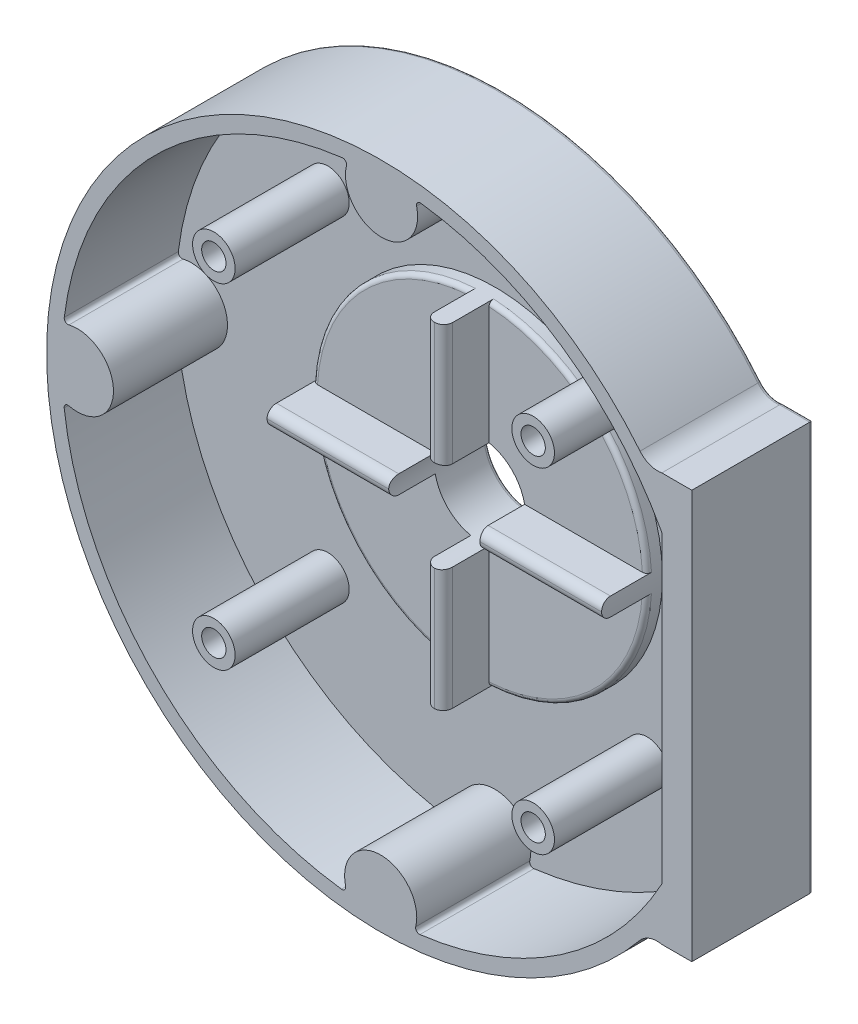
SolidWorks part; units mm, degrees
material "ABS"
ref_plane "Front Plane" through (0, 0, 0) normal (0, 0, 1) x (1, 0, 0)
ref_plane "Top Plane" through (0, 0, 0) normal (0, 1, 0) x (1, 0, 0)
ref_plane "Right Plane" through (0, 0, 0) normal (1, 0, 0) x (0, 0, -1)
sketch "Sketch2" plane through (0, 0, 0) normal (0, 0, 1) x (1, 0, 0)
  circle A0 centre (0, 0) radius 22
  dimension "D1" = 44
extrude "Boss-Extrude1" add sketch "Sketch2" along normal blind 8
sketch "Sketch3" plane through (0, 0, 8) normal (0, 0, 1) x (1, 0, 0)
  circle A0 centre (0, 0) radius 21
  dimension "D1" = 42
extrude "Cut-Extrude2" cut sketch "Sketch3" against normal blind 7.5
sketch "Sketch4" plane through (0, 0, 0.5) normal (0, 0, 1) x (1, 0, 0)
  line L0 (-11, -11.015) -> (10, -11.015) construction
  line L1 (-11, 11) -> (10, 11) construction
  line L2 (10, 11) -> (10, -11.015) construction
  line L3 (-11, 11) -> (0, 0) construction
  line L4 (0, 0) -> (10, -11.015) construction
  line L5 (10, 11) -> (0, 0) construction
  line L6 (0, 0) -> (-11, -11.015) construction
  line L8 (-11, 11) -> (-11, -11.015) construction
  circle A0 centre (-11, 11) radius 0.8
  circle A1 centre (10, 11) radius 0.8
  circle A2 centre (10, -11.015) radius 0.8
  circle A3 centre (-11, -11.015) radius 0.8
  circle A4 centre (-11, 11) radius 1.4
  circle A5 centre (10, 11) radius 1.4
  circle A6 centre (10, -11.015) radius 1.4
  circle A7 centre (-11, -11.015) radius 1.4
  dimension "D1" = 1.6
  dimension "D2" = 1.6
  dimension "D3" = 1.6
  dimension "D4" = 1.6
  dimension "D6" = 2.8
  dimension "D7" = 2.8
  dimension "D8" = 2.8
  dimension "D9" = 2.8
  dimension "D5" = 22.015
extrude "Boss-Extrude2" add sketch "Sketch4" along normal up to surface (7.5 mm away) contours A4 A0 | A5 A1 | A6 A2 | A7 A3 region at (-12.3604, 11, 0.5) region at (8.6396, 11, 0.5) region at (8.6396, -11.015, 0.5) region at (-12.3604, -11.015, 0.5) up to face at (21, 0, 8)
sketch "Sketch5" plane through (0, 0, 0.5) normal (0, 0, 1) x (1, 0, 0)
  circle A0 centre (0, 0) radius 3
  dimension "D1" = 6
extrude "Cut-Extrude3" cut sketch "Sketch5" against normal blind 13
sketch "Sketch6" plane through (0, 0, 0.5) normal (0, 0, 1) x (1, 0, 0)
  circle A0 centre (0, 0) radius 3.5
  circle M1 centre (0, 0) radius 3
  dimension "D1" = 7
extrude "Boss-Extrude3" [suppressed] add sketch "Sketch6" along normal blind 5.5 contours A0 M1
sketch "Sketch18" plane through (0, 0, 8) normal (0, 0, 1) x (1, 0, 0)
  circle A0 centre (-11, 11) radius 0.8
  circle A1 centre (10, 11) radius 0.8
  circle A2 centre (10, -11.015) radius 0.8
  circle A3 centre (-11, -11.015) radius 0.8
extrude "Cut-Extrude7" cut sketch "Sketch18" against normal through all
sketch "Sketch20" plane through (0, 0, 8) normal (0, 0, 1) x (1, 0, 0)
  line L5 (17.3708, 11.4007) -> (27.4615, 11.4007)
  line L6 (17.3708, 11.4007) -> (17.3708, -11.4529)
  line L7 (17.3708, -11.4529) -> (27.4615, -11.4529)
  line L8 (27.4615, 11.4007) -> (27.4615, -11.4529)
extrude "Cut-Extrude8" cut sketch "Sketch20" against normal blind 5
sketch "Sketch23" plane through (0, 0, 0.5) normal (0, 0, 1) x (1, 0, 0)
  arc A2 (-20.8824, 2.2195) -> (-20.8884, -2.1621) centre (0, 0) ccw
  arc A3 (-20.8884, -2.1621) -> (-20.8824, 2.2195) centre (-19.9747, 0.0275) ccw
  arc A4 (-20.8824, 2.2195) -> (-20.8884, -2.1621) centre (0, 0) ccw
  arc A5 (-20.8884, -2.1621) -> (-20.8824, 2.2195) centre (-19.9747, 0.0275) ccw
  arc A6 (-2.2195, -20.8824) -> (2.1621, -20.8884) centre (0, 0) ccw
  arc A7 (2.1621, -20.8884) -> (-2.2195, -20.8824) centre (-0.0275, -19.9747) ccw
  arc A8 (-2.2195, -20.8824) -> (2.1621, -20.8884) centre (0, 0) ccw
  arc A9 (2.1621, -20.8884) -> (-2.2195, -20.8824) centre (-0.0275, -19.9747) ccw
  arc A10 (2.2195, 20.8824) -> (-2.1621, 20.8884) centre (0, 0) ccw
  arc A11 (-2.1621, 20.8884) -> (2.2195, 20.8824) centre (0.0275, 19.9747) ccw
  arc A12 (2.2195, 20.8824) -> (-2.1621, 20.8884) centre (0, 0) ccw
  arc A13 (-2.1621, 20.8884) -> (2.2195, 20.8824) centre (0.0275, 19.9747) ccw
  dimension "D1" = 0
  dimension "D2" = 0
  dimension "D3" = 0
extrude "Boss-Extrude10" add sketch "Sketch23" along normal up to surface (7.5 mm away) up to face at (-1.6453, 0.0024, 8)
fillet "Fillet2" radius 0.25 6 edges at (-2.2195, -20.8824, 4.25) (2.2195, 20.8824, 4.25) (-2.1621, 20.8884, 4.25) (-20.8824, 2.2195, 4.25) (-20.8884, -2.1621, 4.25) (2.1621, -20.8884, 4.25)
sketch3d "3DSketch3" plane through (0, 0, 0) normal (0, 0, 1) x (1, 0, 0)
  dimension "D1" = 25
sketch "Sketch24" plane through (20.4592, 0, 0) normal (1, 0, 0) x (0, 0, -1)
  line L0 (-8, 11.4007) -> (-3, 11.4007) construction
  line L5 (-3, -11.4529) -> (-8, -11.4529) construction
  line L6 (-8, 11.4007) -> (-3, 11.4007)
  line L7 (-3, -11.4529) -> (-8, -11.4529)
  line L8 (-8, -11.4529) -> (-8, -13.4529)
  line L9 (-8, -13.4529) -> (0, -13.4529)
  line L10 (0, -13.4529) -> (0, 13.4007)
  line L11 (0, 13.4007) -> (-8, 13.4007)
  line L12 (-8, 13.4007) -> (-8, 11.4007)
  line L13 (-3, 11.4007) -> (-3, -11.4529)
  line L14 (0, -22) -> (0, 22) construction
  dimension "D1" = 2
  dimension "D2" = 2
extrude "Boss-Extrude12" add sketch "Sketch24" along normal blind 0.5 and the other way blind 2
fillet "Fillet3" radius 1.5 2 edges at (18.4592, -11.9691, 4) (18.4592, 11.9691, 4)
sketch "Sketch25" plane through (0, 0, 8) normal (0, 0, 1) x (1, 0, 0)
  line L1 (20.4337, 14.3279) -> (34.7, 14.3279)
  line L2 (20.4337, 14.3279) -> (20.4337, -14.1246)
  line L3 (20.4337, -14.1246) -> (34.7, -14.1246)
  line L4 (34.7, 14.3279) -> (34.7, -14.1246)
extrude "Cut-Extrude9" cut sketch "Sketch25" against normal up to next
sketch "Sketch27" plane through (0, 0, 0.5) normal (0, 0, 1) x (1, 0, 0)
  line L1 (18.4592, -10.013) -> (18.4592, 10.013)
  line L3 (18.4592, -10.013) -> (18.4592, 10.013)
  line L4 (18.4592, -10.013) -> (18.4592, 10.013)
  line L6 (1.0142, -4.9794) -> (1.0177, -8.9794)
  line L7 (1.0177, -8.9794) -> (2.5177, -8.9781)
  line L8 (2.5177, -8.9781) -> (2.5142, -4.9781)
  line L9 (2.5142, -4.9781) -> (1.0142, -4.9794)
  line L10 (1.0142, -4.9794) -> (1.0177, -8.9794)
  line L11 (1.0177, -8.9794) -> (2.5177, -8.9781)
  line L12 (2.5177, -8.9781) -> (2.5142, -4.9781)
  line L13 (2.5142, -4.9781) -> (1.0142, -4.9794)
  line L16 (-0.9823, -8.9812) -> (-0.9858, -4.9812)
  line L17 (-2.4823, -8.9825) -> (-0.9823, -8.9812)
  line L18 (-2.4858, -4.9825) -> (-2.4823, -8.9825)
  line L19 (-0.9858, -4.9812) -> (-2.4858, -4.9825)
  line L20 (-0.9823, -8.9812) -> (-0.9858, -4.9812)
  line L21 (-2.4823, -8.9825) -> (-0.9823, -8.9812)
  line L22 (-2.4858, -4.9825) -> (-2.4823, -8.9825)
  line L23 (-0.9858, -4.9812) -> (-2.4858, -4.9825)
  line L24 (-4.9643, 2.5204) -> (-8.9643, 2.5168)
  line L25 (-4.963, 1.0204) -> (-4.9643, 2.5204)
  line L26 (-8.963, 1.0168) -> (-4.963, 1.0204)
  line L27 (-8.9643, 2.5168) -> (-8.963, 1.0168)
  line L28 (-4.9643, 2.5204) -> (-8.9643, 2.5168)
  line L29 (-4.963, 1.0204) -> (-4.9643, 2.5204)
  line L30 (-8.963, 1.0168) -> (-4.963, 1.0204)
  line L31 (-8.9643, 2.5168) -> (-8.963, 1.0168)
  line L32 (-4.9612, -0.9796) -> (-8.9612, -0.9832)
  line L33 (-8.9612, -0.9832) -> (-8.9599, -2.4832)
  line L34 (-8.9599, -2.4832) -> (-4.9599, -2.4796)
  line L35 (-4.9599, -2.4796) -> (-4.9612, -0.9796)
  line L36 (-4.9612, -0.9796) -> (-8.9612, -0.9832)
  line L37 (-8.9612, -0.9832) -> (-8.9599, -2.4832)
  line L38 (-8.9599, -2.4832) -> (-4.9599, -2.4796)
  line L39 (-4.9599, -2.4796) -> (-4.9612, -0.9796)
  line L40 (2.5053, 5.0321) -> (2.5018, 9.0321)
  line L41 (1.0053, 5.0308) -> (2.5053, 5.0321)
  line L42 (1.0018, 9.0308) -> (1.0053, 5.0308)
  line L43 (2.5018, 9.0321) -> (1.0018, 9.0308)
  line L44 (2.5053, 5.0321) -> (2.5018, 9.0321)
  line L45 (1.0053, 5.0308) -> (2.5053, 5.0321)
  line L46 (1.0018, 9.0308) -> (1.0053, 5.0308)
  line L47 (2.5018, 9.0321) -> (1.0018, 9.0308)
  line L48 (-0.9947, 5.029) -> (-0.9982, 9.029)
  line L49 (-0.9982, 9.029) -> (-2.4982, 9.0277)
  line L50 (-2.4982, 9.0277) -> (-2.4947, 5.0277)
  line L51 (-2.4947, 5.0277) -> (-0.9947, 5.029)
  line L52 (-0.9947, 5.029) -> (-0.9982, 9.029)
  line L53 (-0.9982, 9.029) -> (-2.4982, 9.0277)
  line L54 (-2.4982, 9.0277) -> (-2.4947, 5.0277)
  line L55 (-2.4947, 5.0277) -> (-0.9947, 5.029)
  line L56 (5.0171, -2.4708) -> (9.0171, -2.4672)
  line L57 (5.0157, -0.9708) -> (5.0171, -2.4708)
  line L58 (9.0157, -0.9672) -> (5.0157, -0.9708)
  line L59 (9.0171, -2.4672) -> (9.0157, -0.9672)
  line L60 (5.0171, -2.4708) -> (9.0171, -2.4672)
  line L61 (5.0157, -0.9708) -> (5.0171, -2.4708)
  line L62 (9.0157, -0.9672) -> (5.0157, -0.9708)
  line L63 (9.0171, -2.4672) -> (9.0157, -0.9672)
  line L64 (5.014, 1.0292) -> (9.0139, 1.0328)
  line L65 (9.0139, 1.0328) -> (9.0126, 2.5328)
  line L66 (9.0126, 2.5328) -> (5.0126, 2.5292)
  line L67 (5.0126, 2.5292) -> (5.014, 1.0292)
  line L68 (5.014, 1.0292) -> (9.0139, 1.0328)
  line L69 (9.0139, 1.0328) -> (9.0126, 2.5328)
  line L70 (9.0126, 2.5328) -> (5.0126, 2.5292)
  line L71 (5.0126, 2.5292) -> (5.014, 1.0292)
  line L366 (18.4592, -10.013) -> (18.4592, 10.013)
  circle A1 centre (0, 0) radius 3
  circle A2 centre (0, 0) radius 3
  arc A13 (2.5507, -20.8445) -> (18.4592, -10.013) centre (0, 0) ccw
  arc A14 (18.4592, 10.013) -> (2.608, 20.8374) centre (0, 0) ccw
  arc A15 (2.608, 20.8374) -> (2.3339, 20.5308) centre (2.577, 20.5894) ccw
  arc A16 (-2.2774, 20.5371) -> (2.3339, 20.5308) centre (0.0275, 19.9747) ccw
  arc A17 (-2.2774, 20.5371) -> (-2.5507, 20.8445) centre (-2.5203, 20.5964) ccw
  arc A18 (-2.5507, 20.8445) -> (-20.8374, 2.608) centre (0, 0) ccw
  arc A19 (-20.8374, 2.608) -> (-20.5308, 2.3339) centre (-20.5894, 2.577) ccw
  arc A20 (-20.5371, -2.2774) -> (-20.5308, 2.3339) centre (-19.9747, 0.0275) ccw
  arc A21 (-20.5371, -2.2774) -> (-20.8445, -2.5507) centre (-20.5964, -2.5203) ccw
  arc A22 (-20.8445, -2.5507) -> (-2.608, -20.8374) centre (0, 0) ccw
  arc A23 (-2.608, -20.8374) -> (-2.3339, -20.5308) centre (-2.577, -20.5894) ccw
  arc A24 (2.2774, -20.5371) -> (-2.3339, -20.5308) centre (-0.0275, -19.9747) ccw
  arc A25 (2.2774, -20.5371) -> (2.5507, -20.8445) centre (2.5203, -20.5964) ccw
  arc A26 (2.5507, -20.8445) -> (18.4592, -10.013) centre (0, 0) ccw
  arc A27 (18.4592, 10.013) -> (2.608, 20.8374) centre (0, 0) ccw
  arc A28 (2.608, 20.8374) -> (2.3339, 20.5308) centre (2.577, 20.5894) ccw
  arc A29 (-2.2774, 20.5371) -> (2.3339, 20.5308) centre (0.0275, 19.9747) ccw
  arc A30 (-2.2774, 20.5371) -> (-2.5507, 20.8445) centre (-2.5203, 20.5964) ccw
  arc A31 (-2.5507, 20.8445) -> (-20.8374, 2.608) centre (0, 0) ccw
  arc A32 (-20.8374, 2.608) -> (-20.5308, 2.3339) centre (-20.5894, 2.577) ccw
  arc A33 (-20.5371, -2.2774) -> (-20.5308, 2.3339) centre (-19.9747, 0.0275) ccw
  arc A34 (-20.5371, -2.2774) -> (-20.8445, -2.5507) centre (-20.5964, -2.5203) ccw
  arc A35 (-20.8445, -2.5507) -> (-2.608, -20.8374) centre (0, 0) ccw
  arc A36 (-2.608, -20.8374) -> (-2.3339, -20.5308) centre (-2.577, -20.5894) ccw
  arc A37 (2.2774, -20.5371) -> (-2.3339, -20.5308) centre (-0.0275, -19.9747) ccw
  arc A38 (2.2774, -20.5371) -> (2.5507, -20.8445) centre (2.5203, -20.5964) ccw
  arc A41 (2.2774, -20.5371) -> (-2.3339, -20.5308) centre (-0.0275, -19.9747) ccw
  arc A42 (2.2774, -20.5371) -> (2.5507, -20.8445) centre (2.5203, -20.5964) ccw
  arc A43 (2.5507, -20.8445) -> (18.4592, -10.013) centre (0, 0) ccw
  arc A44 (18.4592, 10.013) -> (2.608, 20.8374) centre (0, 0) ccw
  arc A45 (2.608, 20.8374) -> (2.3339, 20.5308) centre (2.577, 20.5894) ccw
  arc A46 (-2.2774, 20.5371) -> (2.3339, 20.5308) centre (0.0275, 19.9747) ccw
  arc A47 (-2.2774, 20.5371) -> (-2.5507, 20.8445) centre (-2.5203, 20.5964) ccw
  arc A48 (-2.5507, 20.8445) -> (-20.8374, 2.608) centre (0, 0) ccw
  arc A49 (-20.8374, 2.608) -> (-20.5308, 2.3339) centre (-20.5894, 2.577) ccw
  arc A50 (-20.5371, -2.2774) -> (-20.5308, 2.3339) centre (-19.9747, 0.0275) ccw
  arc A51 (-20.5371, -2.2774) -> (-20.8445, -2.5507) centre (-20.5964, -2.5203) ccw
  arc A52 (-20.8445, -2.5507) -> (-2.608, -20.8374) centre (0, 0) ccw
  arc A53 (-2.608, -20.8374) -> (-2.3339, -20.5308) centre (-2.577, -20.5894) ccw
  arc A54 (2.2774, -20.5371) -> (-2.3339, -20.5308) centre (-0.0275, -19.9747) ccw
  arc A55 (2.2774, -20.5371) -> (2.5507, -20.8445) centre (2.5203, -20.5964) ccw
  arc A56 (2.5507, -20.8445) -> (18.4592, -10.013) centre (0, 0) ccw
  arc A57 (18.4592, 10.013) -> (2.608, 20.8374) centre (0, 0) ccw
  arc A58 (2.608, 20.8374) -> (2.3339, 20.5308) centre (2.577, 20.5894) ccw
  arc A59 (-2.2774, 20.5371) -> (2.3339, 20.5308) centre (0.0275, 19.9747) ccw
  arc A60 (-2.2774, 20.5371) -> (-2.5507, 20.8445) centre (-2.5203, 20.5964) ccw
  arc A61 (-2.5507, 20.8445) -> (-20.8374, 2.608) centre (0, 0) ccw
  arc A62 (-20.8374, 2.608) -> (-20.5308, 2.3339) centre (-20.5894, 2.577) ccw
  arc A63 (-20.5371, -2.2774) -> (-20.5308, 2.3339) centre (-19.9747, 0.0275) ccw
  arc A64 (-20.5371, -2.2774) -> (-20.8445, -2.5507) centre (-20.5964, -2.5203) ccw
  arc A65 (-20.8445, -2.5507) -> (-2.608, -20.8374) centre (0, 0) ccw
  arc A66 (-2.608, -20.8374) -> (-2.3339, -20.5308) centre (-2.577, -20.5894) ccw
  dimension "D1" = 0
  dimension "D2" = 0
  dimension "D3" = 0
  dimension "D4" = 0
  dimension "D5" = 0
  dimension "D6" = 0
  dimension "D7" = 0
  dimension "D8" = 0
  dimension "D9" = 0
  dimension "D10" = 0
  dimension "D11" = 0
sketch "Sketch29" plane through (0, 0, 0.5) normal (0, 0, 1) x (1, 0, 0)
  circle A0 centre (0, 0) radius 3 construction
  circle A1 centre (0, 0) radius 3
  circle A2 centre (0, 0) radius 10.9998
extrude "Boss-Extrude13" add sketch "Sketch29" along normal blind 1
sketch "Sketch30" plane through (0, 0, 0.5) normal (0, 0, 1) x (1, 0, 0)
  line L0 (-0.6, 12.5) -> (-0.6, 2.9394)
  line L1 (-12.5, -0.6) -> (-2.9394, -0.6)
  line L2 (-12.5, -0.6) -> (-12.5, 0.6)
  line L3 (-12.5, 0.6) -> (-2.9394, 0.6)
  line L4 (12.5, -0.6) -> (12.5, 0.6)
  line L6 (-12.5, 0) -> (-3, 0) construction
  line L7 (-0.6, 12.5) -> (0.6, 12.5)
  line L8 (0.6, 12.5) -> (0.6, 2.9394)
  line L9 (-0.6, -12.5) -> (0.6, -12.5)
  line L11 (0, 12.5) -> (0, 3) construction
  line L12 (12.5, 0.6) -> (2.9394, 0.6)
  line L13 (12.5, 0.6) -> (12.5, -0.6)
  line L14 (12.5, -0.6) -> (2.9394, -0.6)
  line L15 (-12.5, 0.6) -> (-12.5, -0.6)
  line L17 (12.5, 0) -> (3, 0) construction
  line L18 (0.6, -12.5) -> (0.6, -2.9394)
  line L19 (0.6, -12.5) -> (-0.6, -12.5)
  line L20 (-0.6, -12.5) -> (-0.6, -2.9394)
  line L21 (0.6, 12.5) -> (-0.6, 12.5)
  line L23 (0, -12.5) -> (0, -3) construction
  line L24 (0.6, 2.9394) -> (0.6, 12.5)
  line L26 (0, 3) -> (0, 12.5) construction
  line L28 (-0.6, 2.9394) -> (-0.6, 12.5)
  line L30 (-2.9394, 0.6) -> (-12.5, 0.6)
  line L32 (-3, 0) -> (-12.5, 0) construction
  line L34 (-2.9394, -0.6) -> (-12.5, -0.6)
  line L37 (-0.6, -2.9394) -> (-0.6, -12.5)
  line L39 (0, -3) -> (0, -12.5) construction
  line L41 (0.6, -2.9394) -> (0.6, -12.5)
  line L43 (2.9394, -0.6) -> (12.5, -0.6)
  line L45 (3, 0) -> (12.5, 0) construction
  line L47 (2.9394, 0.6) -> (12.5, 0.6)
  circle A0 centre (0, 0) radius 3 construction
  circle A1 centre (0, 0) radius 3
  point P0 (0, 0)
  point P7 (0, 0)
  point P16 (0, 0)
  point P25 (0, 0)
  circle M23 centre (0, 0) radius 10.9998
  dimension "D1" = 1.2
  dimension "D2" = 25
  dimension "D3" = 4
extrude "Boss-Extrude15" add sketch "Sketch30" along normal blind 4 contours L3 L8 L1 M23 | A1 L20 L18 M23 | A1 L14 L12 M23 | A1 L8 L0 M23 | L3 L4 L1 L2 | L0 L9 L8 L7 region at (0, 6.9871, 0.5) region at (-6.9871, 0, 0.5) region at (6.9871, 0, 0.5) region at (0, -6.9871, 0.5)
sketch "Sketch31" plane through (0, 0, 3) normal (0, 0, 1) x (1, 0, 0)
  line L4 (20.4337, -11.4529) -> (20.4337, 11.4007)
  line L5 (20.4337, 11.4007) -> (17.6359, 11.4007)
  line L6 (18.4592, 10.013) -> (18.4592, -10.013)
  line L7 (17.602, -11.4529) -> (20.4337, -11.4529)
  line L8 (20.4337, -11.4529) -> (20.4337, 11.4007)
  line L9 (20.4337, 11.4007) -> (17.6359, 11.4007)
  line L10 (18.4592, 10.013) -> (18.4592, -10.013)
  line L11 (17.602, -11.4529) -> (20.4337, -11.4529)
  arc A2 (18.4592, 10.013) -> (17.6359, 11.4007) centre (0, 0) ccw
  arc A3 (17.602, -11.4529) -> (18.4592, -10.013) centre (0, 0) ccw
  arc A4 (18.4592, 10.013) -> (17.6359, 11.4007) centre (0, 0) ccw
  arc A5 (17.602, -11.4529) -> (18.4592, -10.013) centre (0, 0) ccw
  dimension "D1" = 0
extrude "Boss-Extrude16" add sketch "Sketch31" along normal up to surface (5 mm away) up to face at (2.9367, -0.0035, 8)
sketch "Sketch32" plane through (0, 0, 0) normal (0, 0, -1) x (-1, 0, 0)
  circle A0 centre (0, 0) radius 3 construction
  circle A1 centre (0, 0) radius 3
  circle A2 centre (0, 0) radius 11
extrude "Boss-Extrude18" add sketch "Sketch32" along normal blind 2
fillet "Fillet4" radius 0.25 1 edges at (-11, 0, -2)
fillet "Fillet5" radius 0.25 1 edges at (-3, 0, -2)
fillet "Fillet6" radius 0.25 6 edges at (17.6731, 13.4691, 0) (19.4464, 13.4007, 0) (20.4337, -0.0261, 0) (19.4464, -13.4529, 0) (17.6556, -13.5072, 0) (-22, 0.0273, 0)
fillet "Fillet10" radius 0.6 8 edges at (-0.6, 6.9614, 4.5) (0.6, 6.9614, 4.5) (-6.9614, -0.6, 4.5) (-6.9614, 0.6, 4.5) (-0.6, -6.9614, 4.5) (0.6, -6.9614, 4.5) (6.9614, -0.6, 4.5) (6.9614, 0.6, 4.5)
fillet "Fillet11" radius 0.3 4 edges at (-7.778, 7.778, 1.5) (-7.778, -7.778, 1.5) (7.778, 7.778, 1.5) (7.778, -7.778, 1.5)
